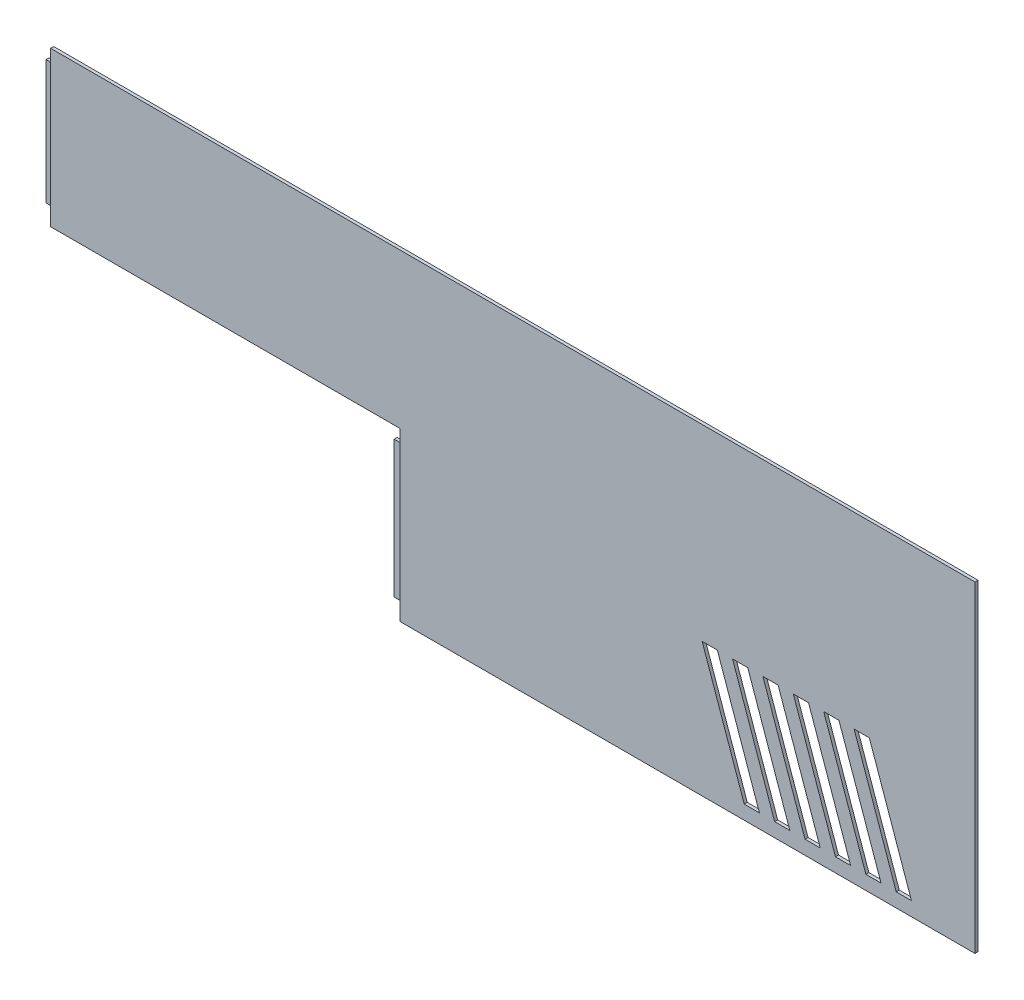
SolidWorks part; units mm, degrees
ref_plane "Plan de face" through (0, 0, 0) normal (0, 0, 1) x (1, 0, 0)
ref_plane "Plan de dessus" through (0, 0, 0) normal (0, 1, 0) x (1, 0, 0)
ref_plane "Plan de droite" through (0, 0, 0) normal (1, 0, 0) x (0, 0, -1)
sketch "Esquisse1" plane through (0, 0, 0) normal (0, 0, 1) x (1, 0, 0)
  line L1 (-318.4, 56.6) -> (-203.4, 56.6)
  line L2 (-203.4, 56.6) -> (-203.4, 1.6)
  line L3 (-203.4, 1.6) -> (-14.3508, 1.6)
  line L4 (-14.3508, 1.6) -> (-14.3508, 107.4388)
  line L5 (-14.3508, 107.4388) -> (-318.4, 107.4388)
  line L6 (-318.4, 107.4388) -> (-318.4, 56.6)
  line L7 (-203.4, 1.6) -> (-14.3508, 1.6) construction
  line L8 (-14.3508, 107.4388) -> (-14.3508, 1.6) construction
  point P0 (-14.3508, 1.6)
  point P5 (-319, 56)
  point P9 (-318.4, 56.6)
  point P10 (0, 0)
extrude "Boss.-Extru.1" add sketch "Esquisse1" against normal blind 1
sketch "Esquisse2" plane through (0, 0, -1) normal (0, 0, -1) x (-1, 0, 0)
  line L1 (315.9215, 102.4388) -> (320.9215, 102.4388)
  line L2 (315.9215, 102.4388) -> (315.9215, 61.6)
  line L3 (315.9215, 61.6) -> (320.9215, 61.6)
  line L4 (320.9215, 102.4388) -> (320.9215, 61.6)
  line L5 (201.4, 51.6) -> (206.4, 51.6)
  line L6 (201.4, 51.6) -> (201.4, 6.6)
  line L7 (201.4, 6.6) -> (206.4, 6.6)
  line L8 (206.4, 51.6) -> (206.4, 6.6)
  line L10 (203.4, 56.6) -> (203.4, 1.6) construction
  line L12 (14.3508, 107.4388) -> (318.4, 107.4388) construction
  line L13 (318.4, 56.6) -> (203.4, 56.6) construction
  line L14 (203.4, 1.6) -> (14.3508, 1.6) construction
  dimension "D1" = 5
  dimension "D2" = 5
  dimension "D3" = 2
  dimension "D4" = 5
  dimension "D5" = 5
  dimension "D6" = 5
  dimension "D7" = 5
extrude "Boss.-Extru.2" add sketch "Esquisse2" along normal blind 1
sketch "Esquisse3" plane through (0, 0, -1) normal (0, 0, -1) x (-1, 0, 0)
  line L0 (19.3508, 56.6) -> (155.1, 56.6) construction
  line L1 (24.3508, 56.6) -> (150.1, 56.6)
  line L2 (24.3508, 56.6) -> (24.3508, 58.6)
  line L3 (24.3508, 58.6) -> (150.1, 58.6)
  line L4 (150.1, 56.6) -> (150.1, 58.6)
  line L5 (19.3508, 55) -> (155.1, 55) construction
  line L6 (24.3508, 55) -> (150.1, 55)
  line L7 (24.3508, 55) -> (24.3508, 53)
  line L8 (24.3508, 53) -> (150.1, 53)
  line L9 (150.1, 55) -> (150.1, 53)
  line L10 (180.4, 56.6) -> (203.4, 56.6) construction
  line L11 (185.4, 56.6) -> (198.4, 56.6)
  line L12 (185.4, 56.6) -> (185.4, 58.6)
  line L13 (185.4, 58.6) -> (198.4, 58.6)
  line L14 (198.4, 56.6) -> (198.4, 58.6)
  line L15 (203.4, 55) -> (180.4, 55) construction
  line L16 (185.4, 55) -> (198.4, 55)
  line L17 (185.4, 55) -> (185.4, 53)
  line L18 (185.4, 53) -> (198.4, 53)
  line L19 (198.4, 55) -> (198.4, 53)
  line L21 (19.3508, 55) -> (19.3508, 1.6) construction
  line L22 (203.4, 56.6) -> (203.4, 51.6) construction
  line L23 (155.1, 56.6) -> (155.1, 55) construction
  line L24 (180.4, 55) -> (180.4, 56.6) construction
  dimension "D1" = 5
  dimension "D2" = 5
  dimension "D4" = 2
  dimension "D6" = 5
  dimension "D7" = 5
extrude "Boss.-Extru.3" add sketch "Esquisse3" along normal blind 2
chamfer "Chanfrein1" distance 1.5 angle 45 4 edges at (-191.9, 53, -3) (-191.9, 58.6, -3) (-87.2254, 53, -3) (-87.2254, 58.6, -3)
chamfer "Chanfrein2" distance 1 angle 45 2 edges at (-201.4, 29.1, -1) (-315.9215, 82.0194, -1)
sketch "Esquisse4" plane through (0, 0, -1) normal (0, 0, -1) x (-1, 0, 0)
  line L0 (90.2455, 6.2064) -> (85.2455, 6.2064)
  line L1 (85.2455, 6.2064) -> (99.0945, 45.6513)
  line L2 (99.0945, 45.6513) -> (104.0945, 45.6513)
  line L3 (104.0945, 45.6513) -> (90.2455, 6.2064)
  line L4 (94.0945, 45.6513) -> (80.2455, 6.2064)
  line L5 (80.2455, 6.2064) -> (75.2455, 6.2064)
  line L6 (75.2455, 6.2064) -> (89.0945, 45.6513)
  line L7 (89.0945, 45.6513) -> (94.0945, 45.6513)
  line L8 (84.0945, 45.6513) -> (70.2455, 6.2064)
  line L9 (70.2455, 6.2064) -> (65.2455, 6.2064)
  line L10 (65.2455, 6.2064) -> (79.0945, 45.6513)
  line L11 (79.0945, 45.6513) -> (84.0945, 45.6513)
  line L12 (74.0945, 45.6513) -> (60.2455, 6.2064)
  line L13 (60.2455, 6.2064) -> (55.2455, 6.2064)
  line L14 (55.2455, 6.2064) -> (69.0945, 45.6513)
  line L15 (69.0945, 45.6513) -> (74.0945, 45.6513)
  line L16 (64.0945, 45.6513) -> (50.2455, 6.2064)
  line L17 (50.2455, 6.2064) -> (45.2455, 6.2064)
  line L18 (45.2455, 6.2064) -> (59.0945, 45.6513)
  line L19 (59.0945, 45.6513) -> (64.0945, 45.6513)
  line L20 (54.0945, 45.6513) -> (40.2455, 6.2064)
  line L21 (40.2455, 6.2064) -> (35.2455, 6.2064)
  line L22 (35.2455, 6.2064) -> (49.0945, 45.6513)
  line L23 (49.0945, 45.6513) -> (54.0945, 45.6513)
  point P6 (77.186, 6.2064)
  point P25 (104.0945, 45.6513)
  dimension "D1" = 5
  dimension "D2" = 6
extrude "Enlèv. mat.-Extru.1" cut sketch "Esquisse4" against normal through all
